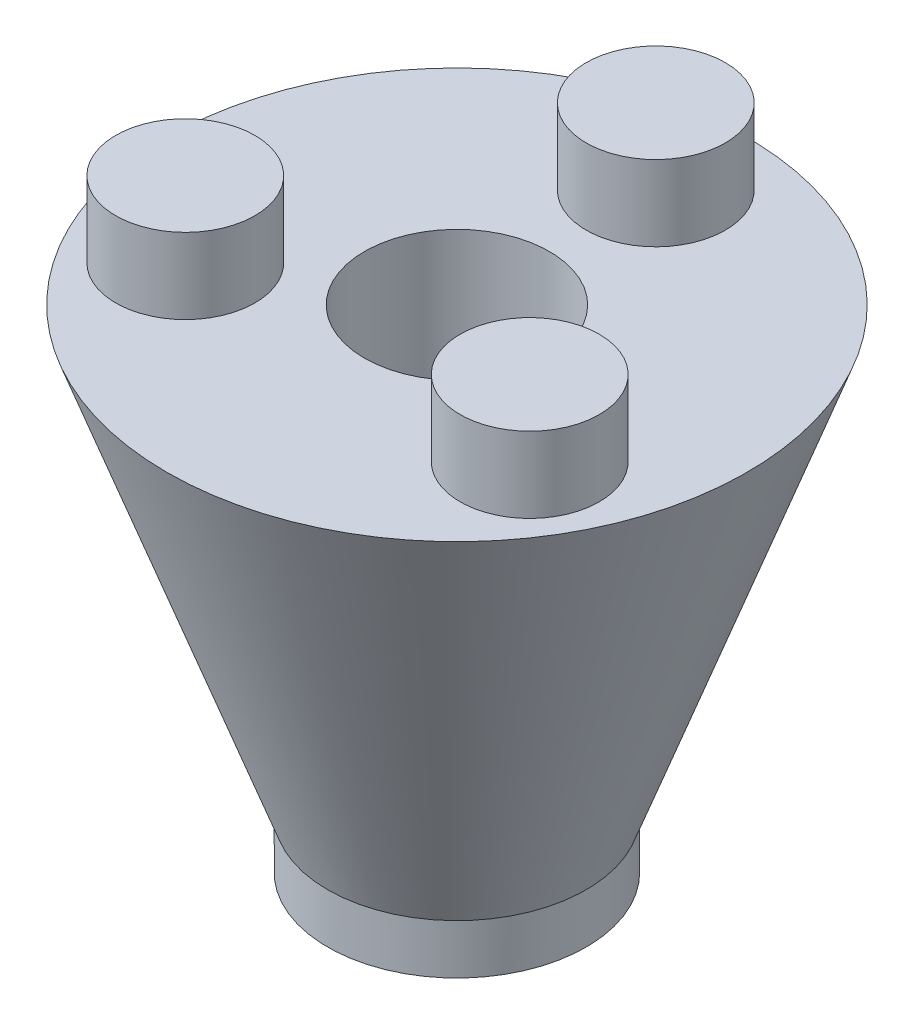
SolidWorks part; units mm, degrees
material "Polyester Resin"
ref_plane "Front Plane" through (0, 0, 0) normal (0, 0, 1) x (1, 0, 0)
ref_plane "Top Plane" through (0, 0, 0) normal (0, 1, 0) x (1, 0, 0)
ref_plane "Right Plane" through (0, 0, 0) normal (1, 0, 0) x (0, 0, -1)
sketch "Sketch1" plane through (0, 0, 0) normal (0, 1, 0) x (1, 0, 0)
  circle A0 centre (0, 0) radius 6.5
  circle A6 centre (0, 0) radius 6.5
  dimension "D7" = 13
extrude "AngleBody" add sketch "Sketch1" along normal blind 22.225 draft 20 contours A0 region at (0, 0, 0) draft outward yes
sketch "Sketch2" plane through (0, 22.225, 0) normal (0, 1, 0) x (1, 0, 0)
  line L0 (-8.6603, -5) -> (8.6603, -5)
  line L1 (8.6603, -5) -> (0, 10)
  line L2 (0, 10) -> (-8.6603, -5)
  circle A0 centre (0, 0) radius 4.65
  circle A1 centre (0, 0) radius 1.935
  circle A2 centre (0, 10) radius 3.5
  circle A3 centre (8.6603, -5) radius 3.5
  circle A4 centre (-8.6603, -5) radius 3.5
  dimension "D1" = 9.3
  dimension "D2" = 3.87
  dimension "D5" = 7
  dimension "D3" = 10
  dimension "D4" = 10
extrude "CenterHole" cut sketch "Sketch2" against normal through all contours A1 | A0 A1 region at (-4.5185, 22.225, 0) region at (0, 22.225, 0)
extrude "40tPegs" add sketch "Sketch2<3>" along normal blind 3.8 contours L1 A2 L2 | L2 A2 L1 | L0 A4 L2 | L2 A4 L0 | L1 A3 L0 | L0 A3 L1 region at (-6.7306, 22.225, 3.8859) region at (-9.0462, 22.225, 5.2228) region at (6.7306, 22.225, 3.8859) region at (9.0462, 22.225, 5.2228) region at (0, 22.225, -10.4456) region at (0, 22.225, -7.7718)
sketch "Sketch2<3>" plane through (0, 22.225, 0) normal (0, 1, 0) x (1, 0, 0) same geometry as "Sketch2"
sketch "Sketch3" plane through (0, 0, 0) normal (0, -1, 0) x (1, 0, 0)
  circle A0 centre (0, 0) radius 6.5 construction
  circle A2 centre (0, 0) radius 6.5
  circle A3 centre (0, 0) radius 3.3
  dimension "D1" = 6.6
extrude "20tInterface" add sketch "Sketch3" along normal blind 2.5
equation "\"CageLeftBottomEdge\"=22.11mm"
equation "\"CageLeftTopEdge\"=22.11mm"
equation "\"CageRightBottomEdge\"=21.63mm"
equation "\"CageRightTopEdge\"=21.63mm"
equation "\"CageHeight\"=86.04mm"
equation "\"CageLength\"=73.76mm"
equation "\"CageTopScrewClearance\"=10mm"
equation "\"CageBottomScrewClearance\"=25mm"
equation "\"CageLeftTopDepth\"= 11.65mm"
equation "\"CageLeftBottomDepth\"=11.11mm"
equation "\"CageLeftTopHeight\"=8.56175mm"
equation "\"CageLeftBottomHeight\"=16mm"
equation "\"CageRightTopDepth\"= 11.05mm"
equation "\"CageRightBottomDepth\"=10.58mm"
equation "\"CageRightTopHeight\"=9.6mm"
equation "\"CageRightBottomHeight\"=15.49mm"
equation "\"CageLeftTopChannelDepth\"=2.41908mm"
equation "\"CageLeftBottomChannelDepth\"=2.588mm"
equation "\"CageLeftChannelHeight\"=11.7mm"
equation "\"CageRightTopChannelDepth\"=2.32mm"
equation "\"CageRightBottomChannelDepth\"=2.318mm"
equation "\"CageRightChannelHeight\"=10mm"
equation "\"CageChanRelHeight\"=23.99mm"
equation "\"CageChanRelDepth\"=5.492mm"
equation "\"CageChamberRadius\"=16.261mm"
equation "\"CageScrewDiameter\"=4.8mm"
equation "\"CageSetScrewDiameter\"=3.5mm"
equation "\"CageAxleRadius\"=6.639mm"
equation "\"CageAxleKeyHeight\"=1.619mm"
equation "\"CageAxleKeyWidth\"=2.662mm"
equation "\"CageHoseWindowWidth\"=16.29mm"
equation "\"CageHoseWindowHeight\"=26.5mm"
equation "\"CageHoseWindow-Edge\"=8.89mm"
equation "\"CageScrew-VerticalEdge\"=5.0mm"
equation "\"CageScrew-HorizontalEdge\"=7.5mm"
equation "\"CageScrew-HoseCornerScrewEdge\"=4.45mm"
equation "\"CageAxle-BottomEdge\"=56.05mm"
equation "\"CageAxle-FrontEdge\"=46.03mm"
equation "\"CageBackSetScrew-Axle\"=40mm"
equation "\"CageFrontSetScrew-Axle\"=22mm"
equation "\"CageVelocityWindow-BackEdge\"=34.8mm"
equation "\"CageVelocityWindow-BottomEdge\"=27.55mm"
equation "\"CageVelocityWindowHeight\"=22.29mm"
equation "\"CageVelocityWindowWidth\"=12.61mm"
equation "\"TriggerSlot-BottomEdge\"=6.35mm"
equation "\"TriggerSlot-FrontEdge\"=15mm"
equation "\"TriggerSlotSize\"=6.7mm"
equation "\"TriggerRackOffset\"=.236224in"
equation "\"TriggerSlotSizeInt\"=.25in"
equation "\"MotorMountLegLength\"=.25in"
equation "\"GearOffset\"=.264907in"
equation "\"TriggerSlotSpacing\"=.25in"
equation "\"TriggerMiniSlotWidth\"=3.5mm"
equation "\"TriggerRackWidth\"=6.5mm"
equation "\"whitemotordepth\"=11.27mm"
equation "\"whitemotorbackdepth\"=3.845mm"
equation "\"whitemotoraxledepth\" = 3.5mm"
equation "\"whitemotoraxleoffset\"=11.4mm"
equation "\"whitemotorwidth\"=12.07mm"
equation "\"whitemotorheight\"=16.68mm"
equation "\"whitemotorcylinderlength\" =13.04mm"
equation "\"whitemotorcylinderradius\"=3.845mm"
equation "\"whitemotorcylinderoffset\"=2.35mm"
equation "\"whitemotorcutoutlength\"=1.88mm"
equation "\"whitemotorouterrad\"=5mm"
equation "\"whitemotorinnerrad\"=2.95mm"
equation "\"elasticracklength\"=2in"
equation "\"elasticrackpegsize\"=.25in"
equation "\"elasticrackpegbuffer\"=.125in"
equation "\"elasticrackpegspacing\"=1.76476378in"
equation "\"elasticbaybuffer\"=.25in"
equation "\"elasticdepth\"=.125in"
equation "\"elasticbaydepth\"=.75in"
equation "\"motormountwidth\"=12mm"
equation "\"motormountcornerfillet\"=3mm"
equation "\"pandiscradius\"=14in"
equation "\"towermaterialwidth\"=.25in"
equation "\"towerslotlength\"=.5in"
equation "\"towermarkerspace\"=5in"
equation "\"towerslothorizoffset\"=1in"
equation "\"towerslothorizspacing\"=2in"
equation "\"towerslotvertoffset\"=3in"
equation "\"towerslotvertspacing\"=1in"
equation "\"towerheight\"=12in"
equation "\"towerupslot\"=1in"
equation "\"toweraxle\"=.5in"
equation "\"stepperouterrad\"=10mm"
equation "\"stepperscrewsize\"=3.45mm"
equation "\"stepperscrewc2c\"=49.5mm"
equation "\"stepperdepthoffset\"=24mm"
equation "\"stepperhorizoffset\"=22.91mm"
equation "\"shaftslotOD\"=18.8mm"
equation "\"shaftslotID\"=13.28mm"
equation "\"shaftkeywidth\"=2.67mm"
equation "\"shaftkeydepth\"=1.8mm"
equation "\"shaftcollartotaldepth\"=12.5mm"
equation "\"shaftsquaredepth\"=6mm"
equation "\"shaftsetscrewsize\"=3.5mm"
equation "\"shaftkeytightdepth\"=1.85mm"
equation "\"shaftslottightID\"=12.78mm"
equation "\"shaftsetscrewoffset\"=9mm"
equation "\"cagecollartotaldepth\"=10mm"
equation "\"cagecollartotalwidth\"=35mm"
equation "\"cagecollarbasedepth\"=4mm"
equation "\"ajaxaxlesize\"=3.87mm"
equation "\"ajax4020gap\"=29.5mm"
equation "\"ajax4010gap\"=24.5mm"
equation "\"shortconangle\"=20deg"
equation "\"D3@AngleBody\"=\"shortconangle\""
equation "\"shortconlen\"=.875in"
equation "\"D1@AngleBody\"=\"shortconlen\""
equation "\"D1@CenterHole\"=\"ajaxhubdepth\"+.1in"
equation "\"D2@Sketch2\"=\"ajaxaxlesize\""
equation "\"ajax40hubholeoffset\"=10mm"
equation "\"D3@Sketch2\"=\"ajax40hubholeoffset\""
equation "\"D4@Sketch2\"=\"ajax40hubholeoffset\""
equation "\"ajax40hubholesize\"=7.21mm"
equation "\"D5@Sketch2\"=\"ajax40hubholesize\"-.21mm"
equation "\"ajaxwidth\"=6.1mm"
equation "\"ajaxcutoutdepth\"=2.3mm"
equation "\"D1@40tPegs\"=\"ajaxwidth\"-\"ajaxcutoutdepth\""
equation "\"ajax20cutoutint\"=13.4mm"
equation "\"D7@Sketch1\"=\"ajax20cutoutint\"-.4mm"
equation "\"ajax40hubbuffer\"=8.9mm"
equation "\"D1@Sketch2\"=\"ajax40hubbuffer\"+.4mm"
equation "\"ajax20hubbuffer\"=6.1mm"
equation "\"D1@Sketch3\"=\"ajax20hubbuffer\"+.5mm"
equation "\"D1@20tInterface\"=\"ajaxcutoutdepth\"+.2mm"
equation "\"gearhubintdiam\"=30mm"
equation "\"gearhubintwid\"=15mm"
equation "\"towerspeedwidth\"=2in"
equation "\"towerspeedheight\"=8in"
equation "\"towerspeedgap\"=2in"
equation "\"stepperaxleflat\"=.037in"
equation "\"stepperaxlerad\"=0.11811024in"
equation "\"ajaxinnercut\"=2.3mm"
equation "\"ajaxdiametral\"=25.8854"
equation "\"ajax20hubholeoffset\"=.19685in"
equation "\"ajax20hubholesize\"=.059055in"
equation "\"ajax40cutoutint\"=32.6mm"
equation "\"bearingpandiscrad\"=6.8in"
equation "\"bearingpandiscang\"=48.75deg"
equation "\"bearingclearholedist\"=4.7345in"
equation "\"bearingclearholesize\"=.5in"
equation "\"bearingclearholeang\"=22.5deg"
equation "\"bearingmountholedist\"=4.25in"
equation "\"bearingwirehole\"=1.5in"
equation "\"no6diam\"=.146in"
equation "\"longconlen\"=1.25in"
equation "\"longconangle\"=15deg"
